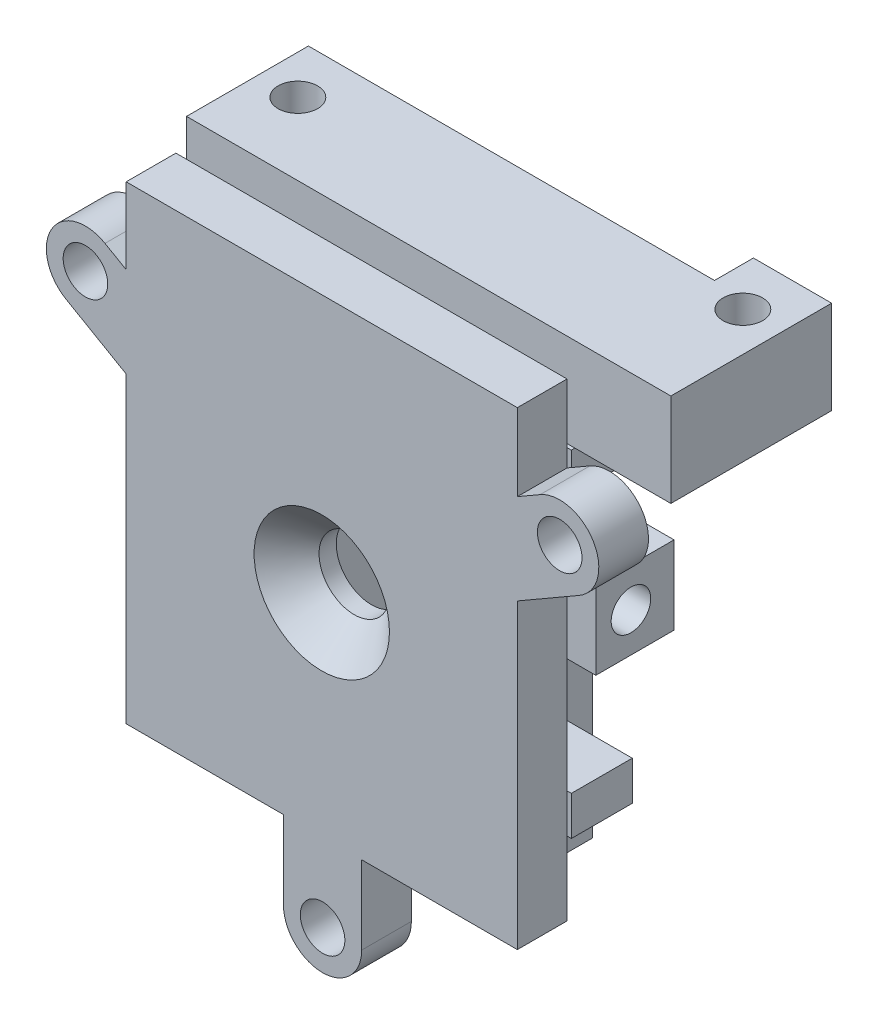
SolidWorks part; units mm, degrees
ref_plane "Front Plane" through (0, 0, 0) normal (0, 0, 1) x (1, 0, 0)
ref_plane "Top Plane" through (0, 0, 0) normal (0, 1, 0) x (1, 0, 0)
ref_plane "Right Plane" through (0, 0, 0) normal (1, 0, 0) x (0, 0, -1)
sketch "Sketch1" plane through (0, 0, 0) normal (0, 0, 1) x (1, 0, 0)
  line L5 (-5, 30) -> (5, 30)
  line L6 (-25, 30) -> (-5, 30)
  line L13 (-25, -30) -> (-4.8977, -30)
  line L31 (5.1023, -30) -> (25, -30)
  line L37 (-4.8977, -30) -> (-4.8977, -40)
  line L39 (5.1023, -30) -> (5.1023, -40)
  line L40 (0.1023, 0) -> (0.1023, -12.7655) construction
  line L41 (0.1023, 0) -> (-30.2086, 17.5) construction
  line L42 (0.1023, 0) -> (30.4132, 17.5) construction
  line L45 (5, 30) -> (25, 30)
  line L61 (25, 30) -> (25, 20.1482)
  line L62 (-25, 30) -> (-25, 20.2663)
  line L63 (-25, 8.7193) -> (-25, -30)
  line L65 (-27.7086, 21.8301) -> (-25, 20.2663)
  line L66 (-32.7086, 13.1699) -> (-25, 8.7193)
  line L67 (27.9132, 21.8301) -> (25, 20.1482)
  line L68 (32.9132, 13.1699) -> (25, 8.6012)
  line L69 (25, 8.6012) -> (25, -30)
  arc A20 (-4.8977, -40) -> (5.1023, -40) centre (0.1023, -40) ccw
  circle A21 centre (0.1023, -40) radius 2.85
  circle A22 centre (30.4132, 17.5) radius 2.85
  circle A23 centre (-30.2086, 17.5) radius 2.85
  arc A29 (-27.7086, 21.8301) -> (-32.7086, 13.1699) centre (-30.2086, 17.5) ccw
  arc A30 (32.9132, 13.1699) -> (27.9132, 21.8301) centre (30.4132, 17.5) ccw
  dimension "D1" = 50
  dimension "D2" = 60
  dimension "D3" = 25
  dimension "D7" = 30
  dimension "D5" = 10
  dimension "D6" = 10
  dimension "D9" = 5
  dimension "D10" = 5.7
  dimension "D11" = 120
  dimension "D12" = 120
  dimension "D13" = 25.1023
  dimension "D15" = 30.3109
  dimension "D14" = 10
  dimension "D17" = 10
  dimension "D16" = 8.9012
  dimension "D4" = 10
  dimension "D8" = 5
  dimension "D18" = 26.4769
  dimension "D19" = 32.1827
  dimension "D20" = 2.7086
  dimension "D21" = 26.4382
  dimension "D22" = 7.9132
  dimension "D23" = 32.1084
  dimension "D24" = 2.9132
extrude "Boss-Extrude1" add sketch "Sketch1" along normal blind 6.35
sketch "Sketch2" plane through (0, 0, 0) normal (0, 0, -1) x (-1, 0, 0)
  line L0 (-12.7, 34.75) -> (12.7, 34.75)
  line L2 (-12.7, 34.75) -> (-12.7, -34.75)
  line L3 (-12.7, -34.75) -> (12.7, -34.75)
  line L4 (12.7, 34.75) -> (12.7, -34.75)
  line L5 (-7.35, 23.4) -> (7.35, 23.4)
  line L6 (-7.35, 23.4) -> (-7.35, -29.4)
  line L7 (-7.35, -29.4) -> (7.35, -29.4)
  line L8 (7.35, 23.4) -> (7.35, -29.4)
  point P8 (-12.7, 0)
  point P13 (0, -34.75)
  dimension "D3" = 14.7
  dimension "D1" = 69.5
  dimension "D2" = 25.4
  dimension "D4" = 5.35
  dimension "D5" = 5.35
  dimension "D6" = 52.8
extrude "Boss-Extrude2" add sketch "Sketch2" along normal blind 15.5784
hole_wizard "CSK for M8 Flat Head Machine Screw1" positions "Sketch3" profile "Sketch4" countersink size "M8" standard "ANSI Metric"
sketch "Sketch3" plane through (0, 0, 6.35) normal (0, 0, 1) x (1, 0, 0)
  point P5 (0, -3)
  dimension "D1" = 3
sketch "Sketch4" plane through (0, -3, 6.35) normal (1, 0, 0) x (0, -1, 0)
  line L0 (0, 0) -> (0, 20.2039)
  line L1 (0, 20.2039) -> (4.5, 17.5)
  line L2 (4.5, 17.5) -> (4.5, 4.15)
  line L3 (4.5, 4.15) -> (8.65, 0)
  line L5 (8.65, 0) -> (0, 0)
  line L6 (-4.5, 4.15) -> (-8.65, 0) construction
  line L10 (0, 20.2039) -> (-4.5, 17.5) construction
  line L11 (0, -6.35) -> (0, 107.95) construction
  dimension "Hole Dia." = 9
  dimension "Hole Depth" = 17.5
  dimension "Near C'Sink Dia." = 17.3
  dimension "Near C'Sink Angle" = 90
  dimension "Drill Angle" = 118
sketch "Sketch6" plane through (12.7, 0, 0) normal (1, 0, 0) x (0, 0, -1)
  line L0 (15.5784, 34.75) -> (15.5784, -34.75) construction
  line L1 (0, 34.75) -> (15.5784, 34.75)
  line L2 (0, 34.75) -> (0, 22.85)
  line L3 (0, 22.85) -> (15.5784, 22.85)
  line L4 (15.5784, 34.75) -> (15.5784, 22.85)
  dimension "D1" = 11.9
extrude "Boss-Extrude3" add sketch "Sketch6" along normal blind 25.5721
sketch "Sketch7" plane through (-12.7, 0, 0) normal (-1, 0, 0) x (0, 0, 1)
  line L1 (-15.5784, 34.75) -> (0, 34.75)
  line L2 (-15.5784, 34.75) -> (-15.5784, 22.85)
  line L3 (-15.5784, 22.85) -> (0, 22.85)
  line L4 (0, 34.75) -> (0, 22.85)
  dimension "D1" = 11.9
extrude "Boss-Extrude4" add sketch "Sketch7" along normal blind 10.9373
sketch "Sketch8" plane through (0, 34.75, 0) normal (0, 1, 0) x (1, 0, 0)
  line L1 (-23.6373, 0) -> (-23.6373, 15.5784) construction
  line L3 (-23.6373, 15.5784) -> (38.2721, 15.5784) construction
  circle A0 centre (-18.6373, 9.2284) radius 2.5273
  dimension "D1" = 5.0546
  dimension "D2" = 6.35
  dimension "D3" = 5
extrude "Cut-Extrude1" cut sketch "Sketch8" against normal blind 7
sketch "Sketch9" plane through (0, 0, -15.5784) normal (0, 0, -1) x (-1, 0, 0)
  line L1 (-38.2721, 34.75) -> (-28.2721, 34.75)
  line L2 (-38.2721, 34.75) -> (-38.2721, 22.85)
  line L3 (-38.2721, 22.85) -> (-28.2721, 22.85)
  line L4 (-28.2721, 34.75) -> (-28.2721, 22.85)
  dimension "D1" = 10
extrude "Boss-Extrude5" add sketch "Sketch9" along normal blind 4.9727
sketch "Sketch10" plane through (0, 34.75, 0) normal (0, 1, 0) x (1, 0, 0)
  line L0 (38.2721, 20.5511) -> (38.2721, 0) construction
  line L1 (28.2721, 20.5511) -> (38.2721, 20.5511) construction
  circle A0 centre (33.2721, 14.2011) radius 2.5273
  circle A1 centre (-18.6373, 9.2284) radius 2.5273 construction
  dimension "D1" = 5
  dimension "D2" = 6.35
extrude "Cut-Extrude2" cut sketch "Sketch10" against normal blind 7
sketch "Sketch11" plane through (12.7, 0, 0) normal (1, 0, 0) x (0, 0, -1)
  line L0 (15.5784, 22.85) -> (15.5784, -34.75) construction
  line L1 (15.5784, -3.175) -> (20.9169, -3.175)
  line L2 (15.5784, -3.175) -> (15.5784, -13.175)
  line L3 (15.5784, -13.175) -> (20.9169, -13.175)
  line L4 (20.9169, -3.175) -> (20.9169, -13.175)
  line L5 (0, 22.85) -> (20.5511, 22.85) construction
  dimension "D1" = 26.025
  dimension "D2" = 10
  dimension "D3" = 5.3384
extrude "Boss-Extrude6" add sketch "Sketch11" against normal up to surface (5.35 mm away) up to face at (7.35, -3, -7.7892)
sketch "Sketch12" plane through (12.7, 0, 0) normal (1, 0, 0) x (0, 0, -1)
  line L1 (14.1276, 4.9) -> (4.1276, 4.9)
  line L2 (14.1276, 4.9) -> (14.1276, -5.1)
  line L3 (14.1276, -5.1) -> (4.1276, -5.1)
  line L4 (4.1276, 4.9) -> (4.1276, -5.1)
  line L5 (0, 22.85) -> (20.5511, 22.85) construction
  line L6 (8.7892, 21.4) -> (1, 21.4)
  line L7 (8.7892, 21.4) -> (8.7892, 16.4)
  line L8 (8.7892, 16.4) -> (1, 16.4)
  line L9 (1, 21.4) -> (1, 16.4)
  line L11 (8.7892, -16.6) -> (1, -16.6)
  line L12 (8.7892, -16.6) -> (8.7892, -21.6)
  line L13 (8.7892, -21.6) -> (1, -21.6)
  line L14 (1, -16.6) -> (1, -21.6)
  line L16 (0, 22.85) -> (0, -30) construction
  point P4 (9.1276, 4.9)
  point P13 (14.1276, -0.1)
  dimension "D1" = 10
  dimension "D2" = 21.5
  dimension "D3" = 7.7892
  dimension "D4" = 5
  dimension "D5" = 43
  dimension "D6" = 5
  dimension "D7" = 1
  dimension "D8" = 8.1276
  dimension "D9" = 10
  dimension "D10" = 1.45
extrude "Boss-Extrude7" add sketch "Sketch12" along normal blind 11.85
sketch "Sketch13" plane through (24.55, 0, 0) normal (1, 0, 0) x (0, 0, -1)
  line L0 (4.1276, 4.9) -> (4.1276, -5.1) construction
  line L1 (4.1276, -5.1) -> (14.1276, -5.1) construction
  circle A0 centre (8.62, -0.1) radius 2.5273
  dimension "D1" = 4.4924
  dimension "D3" = 5.0546
  dimension "D2" = 5
extrude "Cut-Extrude3" cut sketch "Sketch13" against normal blind 7
sketch "Sketch14" plane through (0, 0, -20.9169) normal (0, 0, -1) x (-1, 0, 0)
  line L6 (-12.7, -3.175) -> (-7.35, -3.175)
  line L7 (-12.7, -3.175) -> (-12.7, -13.175)
  line L8 (-12.7, -13.175) -> (-7.35, -13.175)
  line L9 (-7.35, -3.175) -> (-7.35, -13.175)
extrude "Cut-Extrude4" cut sketch "Sketch14" against normal up to surface (5.3384 mm away) up to face at (3.0856, 2.9188, -15.5784)
